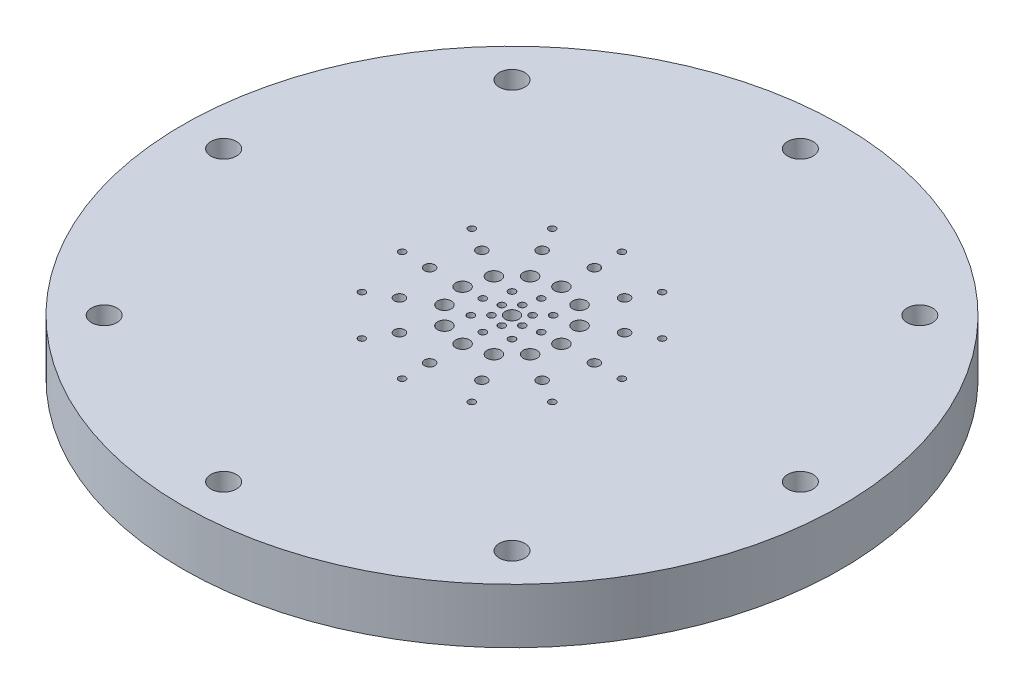
SolidWorks part; units mm, degrees
ref_plane "Front Plane" through (0, 0, 0) normal (0, 0, 1) x (1, 0, 0)
ref_plane "Top Plane" through (0, 0, 0) normal (0, 1, 0) x (1, 0, 0)
ref_plane "Right Plane" through (0, 0, 0) normal (1, 0, 0) x (0, 0, -1)
sketch "Sketch1" plane through (0, 0, 0) normal (0, 1, 0) x (1, 0, 0)
  circle A0 centre (0, 0) radius 38.1
  dimension "D1" = 76.2
extrude "Boss-Extrude1" add sketch "Sketch1" along normal blind 6.35
sketch "Sketch2" plane through (0, 0, 0) normal (0, -1, 0) x (1, 0, 0)
  circle A0 centre (0, 0) radius 33.3375
  circle A1 centre (0, 33.3375) radius 0.762
  dimension "D1" = 66.675
hole_wizard "CBORE for #4 Button Head Cap Screw1" positions "Sketch5" profile "Sketch4" counterbore size "#4" standard "ANSI Inch" end condition through all
sketch "Sketch5" plane through (0, 0, 0) normal (0, -1, 0) x (-1, 0, 0)
  point P0 (0, -33.3375)
sketch "Sketch4" plane through (0, 0, 33.3375) normal (1, 0, 0) x (0, 0, -1)
  line L0 (0, 0) -> (0, 6.35)
  line L1 (0, 6.35) -> (1.4732, 6.35)
  line L3 (1.4732, 6.35) -> (1.4732, 2.8448)
  line L4 (1.4732, 2.8448) -> (2.413, 2.8448)
  line L5 (2.413, 2.8448) -> (2.413, 0)
  line L7 (2.413, 0) -> (0, 0)
  line L11 (0, -6.35) -> (0, 107.95) construction
  dimension "Thru Hole Dia." = 2.9464
  dimension "Thru Hole Depth" = 6.35
  dimension "C'Bore Dia." = 4.826
  dimension "C'Bore Depth" = 2.8448
pattern_circular "CirPattern1" count 8 over 360 about axis through (0, 0, 0) along (0, 1, 0) of "CBORE for #4 Button Head Cap Screw1"
sketch "Sketch6" plane through (0, 6.35, 0) normal (0, 1, 0) x (1, 0, 0)
  circle A0 centre (0, 0) radius 28.575
  dimension "D1" = 57.15
sketch "Sketch7" plane through (0, 0, 0) normal (0, -1, 0) x (1, 0, 0)
  circle A0 centre (0, 12.7) radius 0.3937
  circle A1 centre (0, 9.525) radius 0.5969
  circle A2 centre (0, 5.715) radius 0.8001
  circle A3 centre (0, 0) radius 0.7937
  dimension "D1" = 0.7874
  dimension "D3" = 1.1938
  dimension "D4" = 9.525
  dimension "D5" = 1.6002
  dimension "D6" = 5.715
  dimension "D7" = 1.5875
  dimension "D2" = 12.7
extrude "Cut-Extrude1" cut sketch "Sketch7" against normal through all
pattern_circular "CirPattern3" count 12 over 360 about axis through (0, 0, 0) along (0, 1, 0) of "Cut-Extrude1"
sketch "Sketch8" plane through (0, 6.35, 0) normal (0, 1, 0) x (1, 0, 0)
  circle A0 centre (3.3688, 0) radius 0.3969
  circle A1 centre (2.3821, -2.3821) radius 0.3969
  circle A2 centre (0, -3.3688) radius 0.3969
  circle A3 centre (-2.3821, -2.3821) radius 0.3969
  circle A4 centre (-3.3688, 0) radius 0.3969
  circle A5 centre (-2.3821, 2.3821) radius 0.3969
  circle A6 centre (0, 3.3688) radius 0.3969
  circle A7 centre (2.3821, 2.3821) radius 0.3969
  point P19 (0, 0)
  dimension "D1" = 8
extrude "Cut-Extrude3" cut sketch "Sketch8" against normal up to next
sketch "Sketch9" plane through (0, 6.35, 0) normal (0, 1, 0) x (1, 0, 0)
  line L0 (0, 0) -> (2.3821, 2.3821) construction
  circle A2 centre (1.1877, 1.1877) radius 0.3969
  circle A3 centre (1.6225, -0.4347) radius 0.3969
  circle A4 centre (0.4347, -1.6225) radius 0.3969
  circle A5 centre (-1.1877, -1.1877) radius 0.3969
  circle A6 centre (-1.6225, 0.4347) radius 0.3969
  circle A7 centre (-0.4347, 1.6225) radius 0.3969
  point P18 (0, 0)
  dimension "D1" = 1.6891
  dimension "D2" = 6
extrude "Cut-Extrude4" cut sketch "Sketch9" against normal up to next
